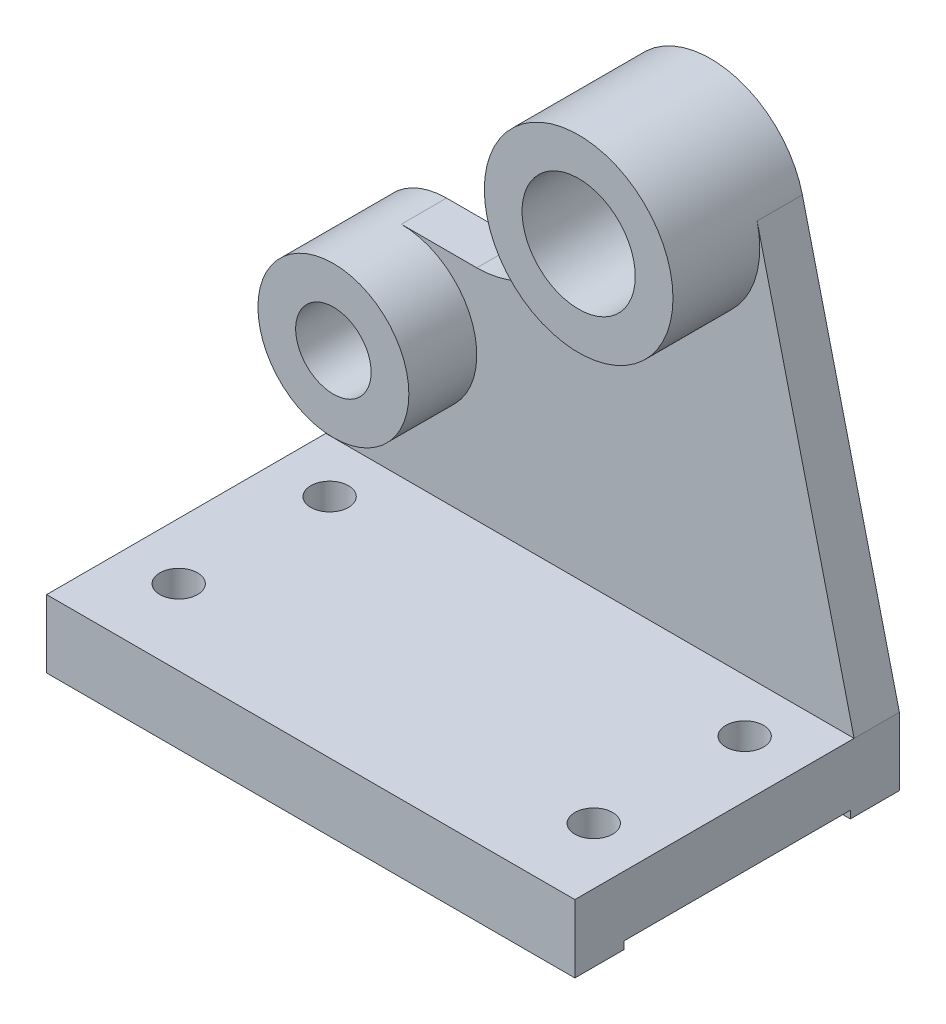
SolidWorks part; units mm, degrees
ref_plane "Front Plane" through (0, 0, 0) normal (0, 0, 1) x (1, 0, 0)
ref_plane "Top Plane" through (0, 0, 0) normal (0, 1, 0) x (1, 0, 0)
ref_plane "Right Plane" through (0, 0, 0) normal (1, 0, 0) x (0, 0, -1)
sketch "Sketch2" plane through (0, 0, 0) normal (0, 0, 1) x (1, 0, 0)
  line L0 (-70, 9) -> (-70, 47)
  line L1 (-70, -9) -> (70, -9)
  line L2 (-70, -9) -> (-70, 9)
  line L3 (-70, 9) -> (70, 9)
  line L4 (70, -9) -> (70, 9)
  line L5 (-70, -9) -> (70, 9) construction
  line L6 (-70, 9) -> (70, -9) construction
  line L7 (70, 9) -> (44.2945, 114.8972)
  line L8 (-50, 67) -> (-30, 67)
  line L9 (-5, 92) -> (-5, 109)
  circle A0 centre (-50, 47) radius 20
  circle A1 centre (-50, 47) radius 10
  circle A2 centre (20, 109) radius 15
  circle A3 centre (20, 109) radius 25
  arc A4 (-5, 92) -> (-30, 67) centre (-30, 92) cw
  point P0 (0, 0)
  dimension "D4" = 20
  dimension "D5" = 40
  dimension "D6" = 30
  dimension "D7" = 50
  dimension "D11" = 25
  dimension "D1" = 20
  dimension "D2" = 140
  dimension "D3" = 18
  dimension "D8" = 56
  dimension "D9" = 50
  dimension "D10" = 118
extrude "Boss-Extrude1" add sketch "Sketch2" along normal blind 86 contours L1 L4 L3 L2 region at (0, 0, 0)
extrude "Boss-Extrude2" add sketch "Sketch2<3>" along normal blind 12 contours L9 A4 L8 A0 L0 L3 L7 A3 region at (9.4951, 43.5701, 0)
sketch "Sketch2<3>" plane through (0, 0, 0) normal (0, 0, 1) x (1, 0, 0) same geometry as "Sketch2"
extrude "Boss-Extrude3" add sketch "Sketch2<4>" along normal blind 35 contours A3 A2 region at (44.1209, 111.8857, 0)
sketch "Sketch2<4>" plane through (0, 0, 0) normal (0, 0, 1) x (1, 0, 0) same geometry as "Sketch2"
extrude "Boss-Extrude4" add sketch "Sketch2<5>" along normal blind 30 contours A0 A1 region at (-63.7421, 60.7421, 0)
sketch "Sketch2<5>" plane through (0, 0, 0) normal (0, 0, 1) x (1, 0, 0) same geometry as "Sketch2"
sketch "Sketch3" plane through (70, 0, 0) normal (1, 0, 0) x (0, 0, -1)
  line L0 (-86, -9) -> (0, -9) construction
  line L1 (-13, -7) -> (-73, -7)
  line L2 (-13, -7) -> (-13, -11)
  line L3 (-13, -11) -> (-73, -11)
  line L4 (-73, -7) -> (-73, -11)
  line L5 (-13, -7) -> (-73, -11) construction
  line L6 (-13, -11) -> (-73, -7) construction
  point P0 (-43, -9)
  dimension "D1" = 60
  dimension "D2" = 4
extrude "Cut-Extrude1" cut sketch "Sketch3" against normal blind 140
sketch "Sketch4" plane through (0, 9, 0) normal (0, 1, 0) x (1, 0, 0)
  line L0 (-70, -86) -> (-70, -12) construction
  line L1 (-70, -86) -> (70, -86) construction
  circle A0 centre (-55, -66) radius 5
  circle A1 centre (55, -66) radius 5
  circle A2 centre (55, -26) radius 5
  circle A3 centre (-55, -26) radius 5
  dimension "D1" = 15
  dimension "D2" = 20
  dimension "D3" = 2
  dimension "D4" = 2
extrude "Cut-Extrude2" cut sketch "Sketch4" against normal blind 140
